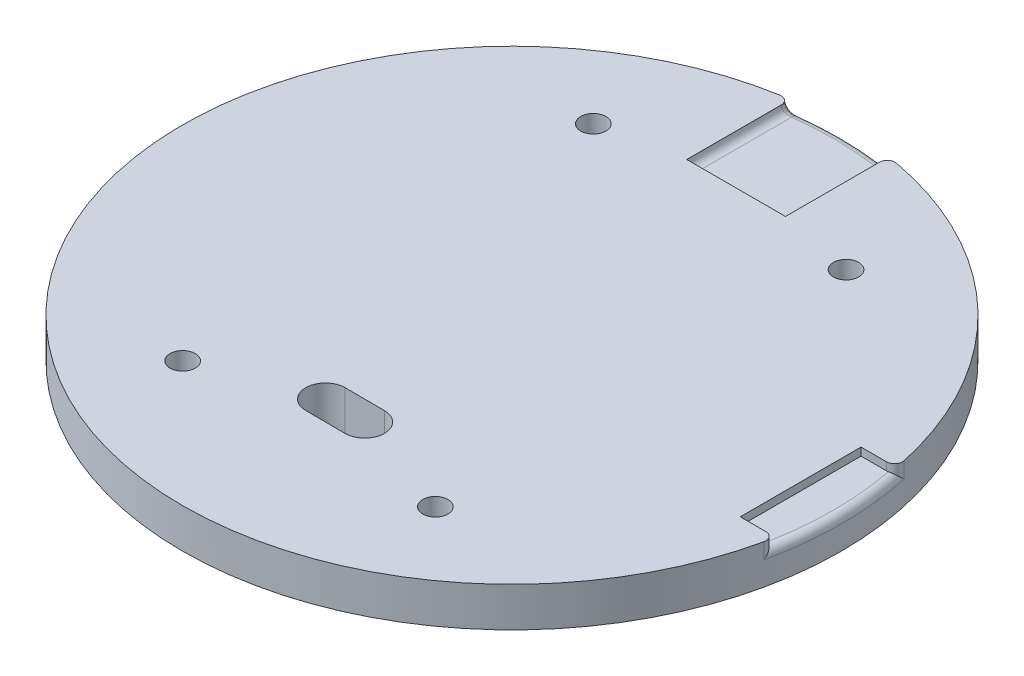
SolidWorks part; units mm, degrees
material "PC High Viscosity"
ref_plane "Front Plane" through (0, 0, 0) normal (0, 0, 1) x (1, 0, 0)
ref_plane "Top Plane" through (0, 0, 0) normal (0, 1, 0) x (1, 0, 0)
ref_plane "Right Plane" through (0, 0, 0) normal (1, 0, 0) x (0, 0, -1)
sketch "Sketch1" plane through (0, 0, 0) normal (0, 1, 0) x (1, 0, 0)
  circle A0 centre (0, 0) radius 41.73
  dimension "D1" = 83.46
extrude "Boss-Extrude1" add sketch "Sketch1" along normal blind 5
sketch "Sketch2" plane through (0, 5, 0) normal (0, 1, 0) x (1, 0, 0)
  circle A0 centre (16.15, -25.85) radius 1.6
  circle A1 centre (16.15, 26.15) radius 1.6
  circle A2 centre (-15.85, 26.15) radius 1.6
  circle A3 centre (-15.85, -25.85) radius 1.6
  circle A4 centre (-15.85, -25.85) radius 1.6 construction
  circle A5 centre (16.15, -25.85) radius 1.6 construction
  circle A6 centre (16.15, 26.15) radius 1.6 construction
  circle A7 centre (-15.85, 26.15) radius 1.6 construction
  dimension "D1" = 3.2
extrude "Cut-Extrude1" cut sketch "Sketch2" against normal blind 4
sketch "Sketch3" plane through (0, 5, 0) normal (0, 1, 0) x (1, 0, 0)
  line L0 (5.4818, 43.05) -> (5.4818, 40) construction
  line L1 (5.4818, 29.15) -> (-5.0182, 29.15) construction
  line L2 (5.4818, 29.15) -> (5.4818, 41.73) construction
  line L3 (5.4818, 41.73) -> (-5.0182, 41.73) construction
  line L4 (-5.0182, 29.15) -> (-5.0182, 41.73) construction
  line L5 (-2.87, 29.15) -> (3.43, 29.15) construction
  line L6 (6.4818, 28.15) -> (6.4818, 42.73)
  line L7 (6.4818, 42.73) -> (-6.0182, 42.73)
  line L8 (-6.0182, 28.15) -> (-6.0182, 42.73)
  line L9 (6.4818, 28.15) -> (-6.0182, 28.15)
  circle A0 centre (0, 0) radius 41.73 construction
  dimension "D1" = 10.5
  dimension "D2" = 1
extrude "Cut-Extrude2" cut sketch "Sketch3" against normal blind 1
fillet "Fillet1" radius 1 3 edges at (6.4818, 4, -34.6868) (-6.0182, 4, -34.7219) (0.2318, 4, -28.15)
sketch "Sketch4" plane through (0, 5, 0) normal (0, 1, 0) x (1, 0, 0)
  line L0 (0, 0) -> (-0.2344, -41.7293) construction
  line L1 (-2.618, -18.5) -> (2.3819, -18.5281)
  line L2 (-2.618, -23.5) -> (2.3819, -23.5281)
  arc A0 (-6.0182, 41.2938) -> (6.4818, 41.2235) centre (0, 0) ccw construction
  circle A1 centre (-2.618, -21) radius 2.5
  circle A2 centre (2.3819, -21.0281) radius 2.5
  dimension "D1" = 5
  dimension "D2" = 5
  dimension "D3" = 21
extrude "Cut-Extrude3" cut sketch "Sketch4" against normal up to surface (5 mm away) contours A1 L1 | A2 L2 | L0 L1 A1 | L1 L0 A2 | L0 A1 L2 | A2 L0 L2 region at (0.4512, 5, 19.0757) region at (-2.618, 5, 21) region at (-0.6655, 5, 19.0694) region at (0.4294, 5, 22.9587) region at (-0.6873, 5, 22.9524) region at (2.3819, 5, 21.0281) up to face at (0, 0, 41.73)
sketch "Sketch5" plane through (0, 5, 0) normal (0, 1, 0) x (1, 0, 0)
  line L0 (41.0413, -7.55) -> (36.65, -7.55) construction
  line L1 (36.65, -7.55) -> (36.65, 7.55) construction
  line L2 (36.65, 7.55) -> (41.0413, 7.55) construction
  line L3 (36.65, -7.55) -> (36.65, 7.55) construction
  line L4 (37.15, -7.55) -> (36.65, -7.55) construction
  line L5 (37.15, 7.55) -> (36.65, 7.55) construction
  line L6 (41.1245, -7.65) -> (36.55, -7.65)
  line L7 (36.55, -7.65) -> (36.55, 7.65)
  line L8 (36.55, 7.65) -> (41.1245, 7.65)
  arc A0 (-6.0182, 41.2938) -> (6.4818, 41.2235) centre (0, 0) ccw construction
  arc A1 (41.0413, -7.55) -> (41.0413, 7.55) centre (0, 0) ccw construction
  arc A2 (41.1245, -7.65) -> (41.1245, 7.65) centre (0, 0) ccw
  dimension "D1" = 0.1
extrude "Cut-Extrude4" cut sketch "Sketch5" against normal blind 1
fillet "Fillet2" radius 1 3 edges at (41.73, 4, 0) (41.0228, 4.5, 7.65) (41.0228, 4.5, -7.65)
fillet "Fillet3" radius 1 3 edges at (-5.8028, 4.38, -41.3246) (6.1111, 4.2229, -41.2801) (0.2336, 4, -41.7293)
